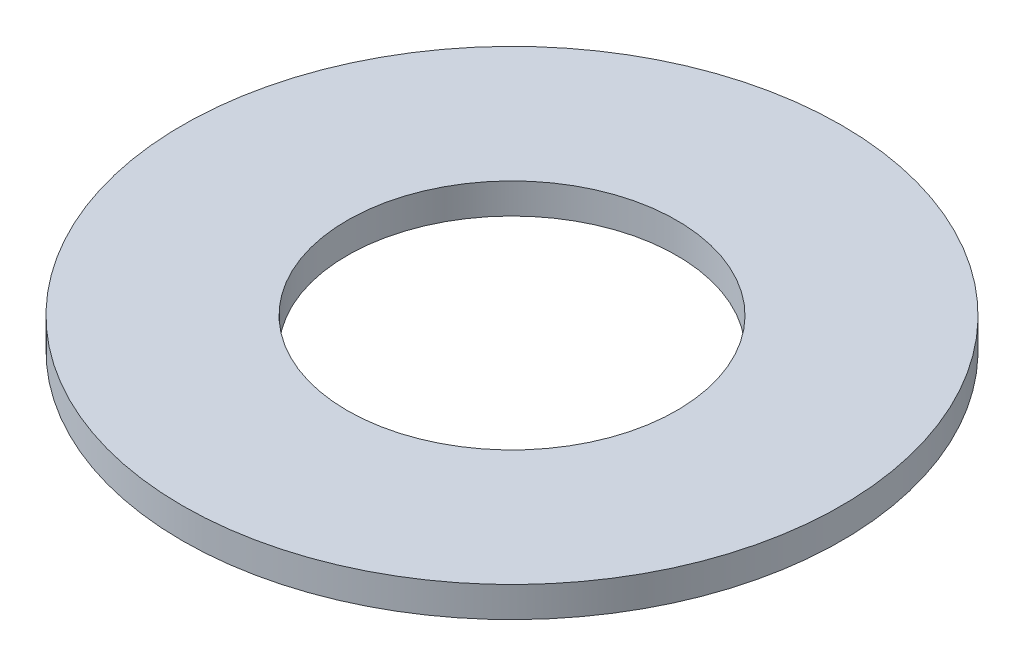
SolidWorks part; units mm, degrees
ref_plane "Front Plane" through (0, 0, 0) normal (0, 0, 1) x (1, 0, 0)
ref_plane "Top Plane" through (0, 0, 0) normal (0, 1, 0) x (1, 0, 0)
ref_plane "Right Plane" through (0, 0, 0) normal (1, 0, 0) x (0, 0, -1)
sketch "Sketch1" plane through (0, 0, 0) normal (0, 1, 0) x (1, 0, 0)
  circle A0 centre (0, 0) radius 65
  dimension "FLANGE_OD" = 130
extrude "Boss-Extrude1" add sketch "Sketch1" along normal blind 6
sketch "Sketch2" plane through (0, 0, 0) normal (0, 1, 0) x (1, 0, 0)
  circle A0 centre (0, 0) radius 32.5
  dimension "BORE_D" = 65
extrude "Cut-Extrude1" cut sketch "Sketch2" along normal through all
sketch "Sketch3" plane through (0, 6, 0) normal (0, 1, 0) x (1, 0, 0)
  circle A0 centre (0, 0) radius 22.4172 construction
  circle A1 centre (-22.4172, 0) radius 1.5797
  dimension "BOLT_D" = 3.1594
  dimension "BOLT_PCD" = 44.8344
extrude "Cut-Extrude2" cut sketch "Sketch3" against normal blind 3.7938 rebuild error yes
pattern_circular "CirPattern1" count 3 over 360 rebuild error yes
